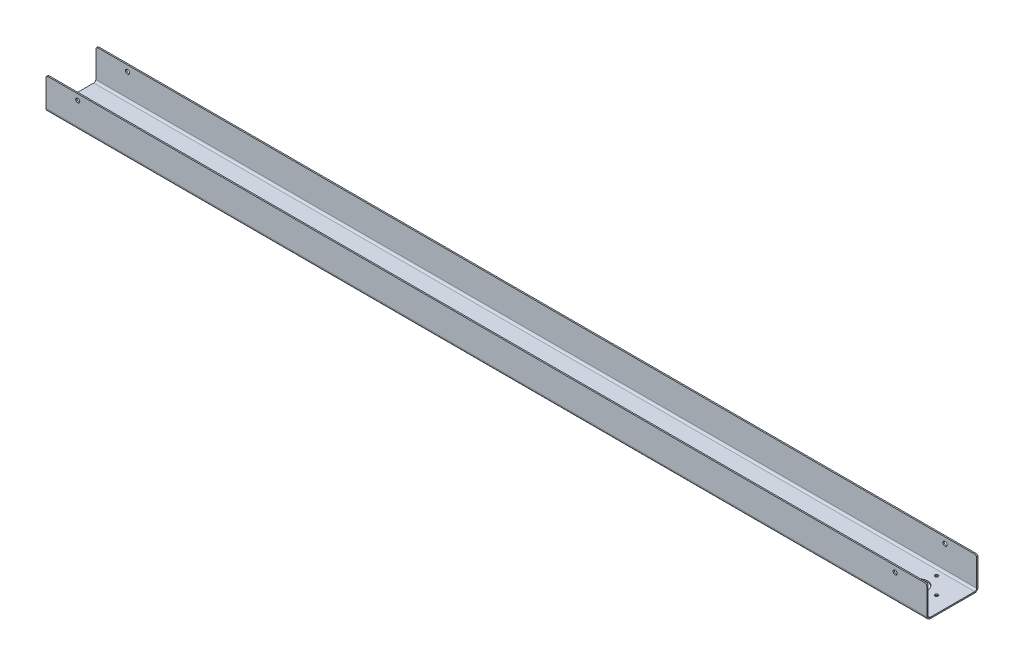
SolidWorks part; units mm, degrees
note: The reader was unsure of these and kept them because the rebuilt part matched: flange length of "Edge-Flange1".
material "5052-O"
ref_plane "Front Plane" through (0, 0, 0) normal (0, 0, 1) x (1, 0, 0)
ref_plane "Top Plane" through (0, 0, 0) normal (0, 1, 0) x (1, 0, 0)
ref_plane "Right Plane" through (0, 0, 0) normal (1, 0, 0) x (0, 0, -1)
sketch "Sketch1" plane through (0, 0, 0) normal (0, 1, 0) x (1, 0, 0)
  line L1 (0, 0) -> (1409.7, 0)
  line L2 (0, 0) -> (0, 81.7563)
  line L3 (0, 81.7563) -> (1409.7, 81.7563)
  line L4 (1409.7, 0) -> (1409.7, 81.7563)
  dimension "D1" = 1409.7
  dimension "D2" = 81.7563
base flange "Base-Flange1" sketch "Sketch1" thickness 2.0526 reverse thickness direction no parameters "D1"=3.175
edge flange "Edge-Flange1" sketch "Sketch10" flange profiles "Sketch10", "Sketch11" flange angle 90 flange length 50.8 flange position material inside bend radius 3.175 thickness 2.0526 relief rectangular parameters "D6"=10, "D8"=1
sketch "Sketch10" plane through (0, 0, 0) normal (0, 0, 1) x (1, 0, 0)
  line L0 (0, 0) -> (1409.7, 0) construction
  line L1 (0, 0) -> (1409.7, 0)
  line L2 (0, 0) -> (0, 48.7474)
  line L3 (0, 48.7474) -> (1409.7, 48.7474)
  line L4 (1409.7, 48.7474) -> (1409.7, 0)
sketch "Sketch11" plane through (0, 0, -81.7563) normal (0, 0, -1) x (-1, 0, 0)
  line L0 (-1409.7, 0) -> (0, 0) construction
  line L1 (-1409.7, 0) -> (0, 0)
  line L2 (-1409.7, 0) -> (-1409.7, 48.7474)
  line L3 (-1409.7, 48.7474) -> (0, 48.7474)
  line L4 (0, 48.7474) -> (0, 0)
bend "EdgeBend1" bend radius 3.175 bend angle 90 parameters "D5"=1
bend "EdgeBend2" bend radius 3.175 bend angle 90 parameters "D5"=2
hole_wizard "#7 (0.201) Diameter Hole1" positions "Sketch12" profile "Sketch13" hole size "#7" standard "ANSI Inch" end condition through all
sketch "Sketch12" plane through (0, -2.0526, 0) normal (0, -1, 0) x (-1, 0, 0)
  line L0 (-1384.3, 40.8781) -> (-1330.325, 40.8781) construction
  line L2 (-1357.3125, 67.8656) -> (-1357.3125, 13.8906) construction
  line L3 (-1409.7, 40.8781) -> (-1454.36, 40.8781) construction
  line L4 (-1409.7, 5.2276) -> (-1409.7, 76.5287) construction
  line L5 (-1409.7, 5.2276) -> (0, 5.2276) construction
  circle A0 centre (-1357.3125, 40.8781) radius 26.9875 construction
  point P0 (-1384.3, 40.8781)
  point P2 (-1330.325, 40.8781)
  point P4 (-1357.3125, 67.8656)
  point P6 (-1357.3125, 13.8906)
  dimension "D1" = 25.4
  dimension "D2" = 26.9875
  dimension "D3" = 35.6506
  dimension "D4" = 26.9875
sketch "Sketch13" plane through (1384.3, -2.0526, -40.8781) normal (1, 0, 0) x (0, 0, -1)
  line L0 (0, 0) -> (0, 50.8)
  line L1 (0, 50.8) -> (2.5527, 50.8)
  line L2 (2.5527, 50.8) -> (2.5527, 0)
  line L5 (2.5527, 0) -> (0, 0)
  line L11 (0, -6.35) -> (0, 107.95) construction
  dimension "Thru Hole Dia." = 5.1054
  dimension "Thru Hole Depth" = 50.8
sketch "Sketch14" plane through (0, 0, 0) normal (0, 0, 1) x (1, 0, 0)
  line L0 (1460.5, 36.0474) -> (0, 36.0474) construction
  line L2 (0, 48.7474) -> (0, 3.175) construction
  line L3 (1409.7, 48.7474) -> (0, 48.7474) construction
  line L4 (127, 31.2849) -> (136.525, 31.2849)
  line L5 (127, 31.2849) -> (127, 40.8099)
  line L6 (127, 40.8099) -> (136.525, 40.8099)
  line L7 (136.525, 31.2849) -> (136.525, 40.8099)
  dimension "D1" = 9.525
  dimension "D2" = 9.525
  dimension "D3" = 127
  dimension "D4" = 12.7
extrude "Cut-Extrude1" [suppressed] cut sketch "Sketch14" against normal through all both and the other way through all
hole_wizard "F (0.257) Diameter Hole1" positions "Sketch15" profile "Sketch16" hole size "F" standard "ANSI Inch" end condition through all
sketch "Sketch15" plane through (0, 0, 0) normal (0, 0, 1) x (1, 0, 0)
  line L0 (0, 48.7474) -> (0, 3.175) construction
  line L1 (1409.7, 3.175) -> (1409.7, 48.7474) construction
  line L2 (1409.7, 48.7474) -> (0, 48.7474) construction
  point P0 (1358.9, 39.2224)
  point P2 (50.8, 39.2224)
  dimension "D1" = 50.8
  dimension "D2" = 50.8
  dimension "D3" = 9.525
  dimension "D4" = 9.525
sketch "Sketch16" plane through (1358.9, 39.2224, 0) normal (1, 0, 0) x (0, -1, 0)
  line L0 (0, 0) -> (0, 81.7563)
  line L1 (0, 81.7563) -> (3.2639, 81.7563)
  line L2 (3.2639, 81.7563) -> (3.2639, 0)
  line L5 (3.2639, 0) -> (0, 0)
  line L11 (0, -6.35) -> (0, 107.95) construction
  dimension "Thru Hole Dia." = 6.5278
  dimension "Thru Hole Depth" = 81.7563
fillet "Fillet1" radius 3.175 4 edges at (1409.7, 48.7474, -1.0263) (1409.7, 48.7474, -80.73) (0, 48.7474, -80.73) (0, 48.7474, -1.0263)
hole_wizard "1 (1) Diameter Hole1" positions "Sketch17" profile "Sketch18" hole size "1" standard "ANSI Inch" end condition through all
sketch "Sketch17" plane through (0, -2.0526, 0) normal (0, -1, 0) x (-1, 0, 0)
  line L0 (-1409.7, 40.8781) -> (-1318.5361, 40.8781) construction
  line L1 (-1409.7, 5.2276) -> (-1409.7, 76.5287) construction
  line L3 (-1357.3125, 13.8906) -> (-1357.3125, 67.8656) construction
  point P12 (-1357.3125, 40.8781)
sketch "Sketch18" plane through (1357.3125, -2.0526, -40.8781) normal (1, 0, 0) x (0, 0, -1)
  line L0 (0, 0) -> (0, 50.8)
  line L1 (0, 50.8) -> (12.7, 50.8)
  line L2 (12.7, 50.8) -> (12.7, 0)
  line L5 (12.7, 0) -> (0, 0)
  line L11 (0, -6.35) -> (0, 107.95) construction
  dimension "Thru Hole Dia." = 25.4
  dimension "Thru Hole Depth" = 50.8
sketch "Bend-Lines1" [suppressed] plane through (0, 0, 0) normal (0, 1, 0) x (1, 0, 0)
sketch "Bounding-Box1" [suppressed] plane through (0, 0, 0) normal (0, 1, 0) x (1, 0, 0)
sheet metal parameters "Sheet-Metal1" thickness 2.0526 parameters "D1"=3.175
flat pattern "Flat-Pattern1" [suppressed]
sketch "Bend-Lines2" plane through (0, 0, 0) normal (0, 1, 0) x (1, 0, 0)
sketch3d "Bounding-Box2" [suppressed]
  line L0 (-1460.5, 82.55, 0) -> (0, 82.55, 0) construction
  line L1 (-1460.5, 0, 0) -> (0, 0, 0) construction
  line L2 (-1460.5, 82.55, 0) -> (-1460.5, 0, 0) construction
  line L3 (0, 82.55, 0) -> (0, 0, 0) construction
sheet metal parameters "Sheet-Metal2" thickness 2.0526 parameters "D1"=3.175
flat pattern "Flat-Pattern1"
sketch "Bend-Lines2" plane through (0, 0, 0) normal (0, 1, 0) x (1, 0, 0)
  line L0 (1460.5, 80.2551) -> (0, 80.2551) construction
  line L1 (0, 2.2949) -> (1460.5, 2.2949) construction
  line L2 (1460.5, 80.2551) -> (0, 80.2551) construction
  line L3 (0, 2.2949) -> (1460.5, 2.2949) construction
sketch3d "Bounding-Box2" [suppressed]
  line L0 (1460.5, 128.7603, 0) -> (0, 128.7603, 0) construction
  line L1 (1460.5, -46.2103, 0) -> (0, -46.2103, 0) construction
  line L2 (1460.5, 128.7603, 0) -> (1460.5, -46.2103, 0) construction
  line L3 (0, 128.7603, 0) -> (0, -46.2103, 0) construction
bend of the flat pattern "Flatten-<EdgeBend1>1"
bend of the flat pattern "Flatten-<EdgeBend2>1"
sheet metal parameters "Sheet-Metal3" thickness 2.0526 parameters "D1"=3.175
flat pattern "Flat-Pattern1"
sketch "Bend-Lines2" plane through (0, 0, 0) normal (0, 1, 0) x (1, 0, 0)
  line L0 (1460.5, 80.2551) -> (0, 80.2551) construction
  line L1 (0, 2.2949) -> (1460.5, 2.2949) construction
  line L2 (1460.5, 80.2551) -> (0, 80.2551) construction
  line L3 (0, 2.2949) -> (1460.5, 2.2949) construction
sketch3d "Bounding-Box2" [suppressed]
  line L0 (1460.5, 128.7603, 0) -> (0, 128.7603, 0) construction
  line L1 (1460.5, -46.2103, 0) -> (0, -46.2103, 0) construction
  line L2 (1460.5, 128.7603, 0) -> (1460.5, -46.2103, 0) construction
  line L3 (0, 128.7603, 0) -> (0, -46.2103, 0) construction
bend of the flat pattern "Flatten-<EdgeBend1>1"
bend of the flat pattern "Flatten-<EdgeBend2>1"
sheet metal parameters "Sheet-Metal4" thickness 2.0526 parameters "D1"=3.175
flat pattern "Flat-Pattern1"
sketch "Bend-Lines2" plane through (0, 0, 0) normal (0, 1, 0) x (1, 0, 0)
  line L0 (1460.5, 80.2551) -> (0, 80.2551) construction
  line L1 (0, 2.2949) -> (1460.5, 2.2949) construction
  line L2 (1460.5, 80.2551) -> (0, 80.2551) construction
  line L3 (0, 2.2949) -> (1460.5, 2.2949) construction
sketch3d "Bounding-Box2" [suppressed]
  line L0 (1460.5, 128.7603, 0) -> (0, 128.7603, 0) construction
  line L1 (1460.5, -46.2103, 0) -> (0, -46.2103, 0) construction
  line L2 (1460.5, 128.7603, 0) -> (1460.5, -46.2103, 0) construction
  line L3 (0, 128.7603, 0) -> (0, -46.2103, 0) construction
bend of the flat pattern "Flatten-<EdgeBend1>1"
bend of the flat pattern "Flatten-<EdgeBend2>1"
sheet metal parameters "Sheet-Metal5" thickness 2.0526 parameters "D1"=3.175
flat pattern "Flat-Pattern1"
sketch "Bend-Lines2" plane through (0, 0, 0) normal (0, 1, 0) x (1, 0, 0)
  line L0 (1409.7, 79.8284) -> (0, 79.8284) construction
  line L1 (0, 1.9279) -> (1409.7, 1.9279) construction
  line L2 (1409.7, 79.8284) -> (0, 79.8284) construction
  line L3 (0, 1.9279) -> (1409.7, 1.9279) construction
sketch3d "Bounding-Box2" [suppressed]
  line L0 (1409.7, 128.7005, 0) -> (0, 128.7005, 0) construction
  line L1 (1409.7, -46.9442, 0) -> (0, -46.9442, 0) construction
  line L2 (1409.7, 128.7005, 0) -> (1409.7, -46.9442, 0) construction
  line L3 (0, 128.7005, 0) -> (0, -46.9442, 0) construction
bend of the flat pattern "Flatten-<EdgeBend1>1"
bend of the flat pattern "Flatten-<EdgeBend2>1"
sheet metal parameters "Sheet-Metal6" thickness 2.0526 parameters "D1"=3.175
flat pattern "Flat-Pattern1"
sketch "Bend-Lines2" plane through (0, 0, 0) normal (0, 1, 0) x (1, 0, 0)
  line L0 (1409.7, 79.8284) -> (0, 79.8284) construction
  line L1 (0, 1.9279) -> (1409.7, 1.9279) construction
  line L2 (1409.7, 79.8284) -> (0, 79.8284) construction
  line L3 (0, 1.9279) -> (1409.7, 1.9279) construction
sketch3d "Bounding-Box2" [suppressed]
  line L0 (1409.7, 128.7005, 0) -> (0, 128.7005, 0) construction
  line L1 (1409.7, -46.9442, 0) -> (0, -46.9442, 0) construction
  line L2 (1409.7, 128.7005, 0) -> (1409.7, -46.9442, 0) construction
  line L3 (0, 128.7005, 0) -> (0, -46.9442, 0) construction
bend of the flat pattern "Flatten-<EdgeBend1>1"
bend of the flat pattern "Flatten-<EdgeBend2>1"
